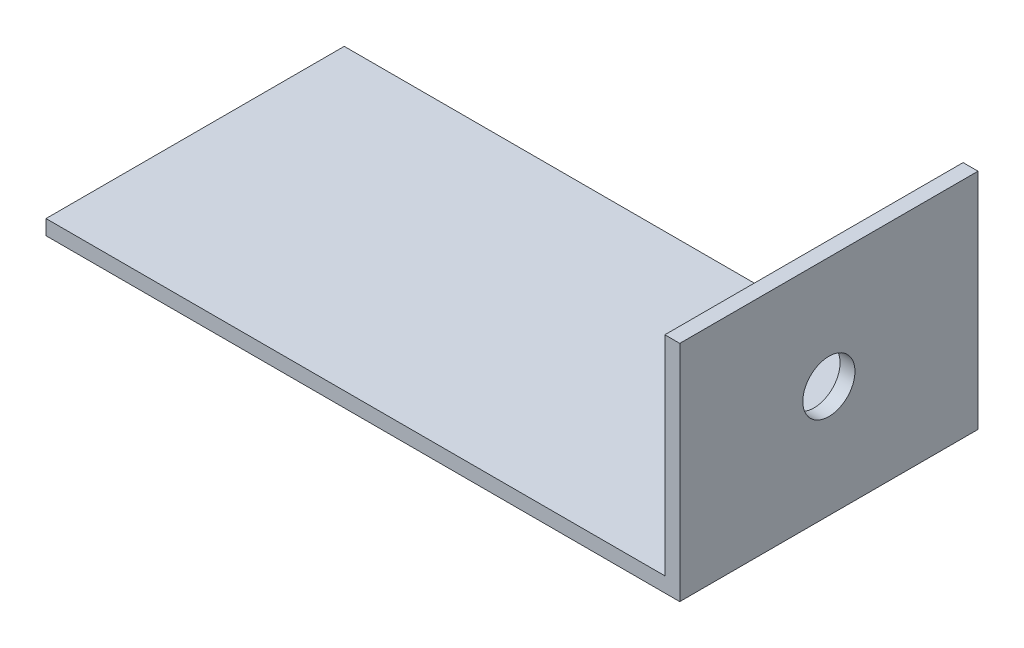
SolidWorks part; units mm, degrees
material "5454-H32"
ref_plane "Alzado" through (0, 0, 0) normal (0, 0, 1) x (1, 0, 0)
ref_plane "Planta" through (0, 0, 0) normal (0, 1, 0) x (1, 0, 0)
ref_plane "Vista lateral" through (0, 0, 0) normal (1, 0, 0) x (0, 0, -1)
sketch "Croquis1" plane through (0, 0, 0) normal (0, 0, 1) x (1, 0, 0)
  line L0 (0.5514, 28.1831) -> (0.5514, -1.8169)
  line L1 (0.5514, 28.1831) -> (-1.4486, 28.1831)
  line L2 (-1.4486, 28.1831) -> (-1.4486, 0.1831)
  line L3 (-1.4486, 0.1831) -> (-84.4486, 0.1831)
  line L4 (-84.4486, 0.1831) -> (-84.4486, -1.8169)
  line L5 (-84.4486, -1.8169) -> (0.5514, -1.8169)
  dimension "D1" = 2
  dimension "D2" = 30
  dimension "D3" = 85
extrude "Saliente-Extruir1" add sketch "Croquis1" along normal blind 40
sketch "Croquis2" plane through (0.5514, 0, 0) normal (1, 0, 0) x (0, 0, -1)
  line L0 (-40, 28.1831) -> (0, -1.8169) construction
  circle A0 centre (-20, 13.1831) radius 3.5
  dimension "D1" = 7
extrude "Cortar-Extruir1" cut sketch "Croquis2" against normal through all
